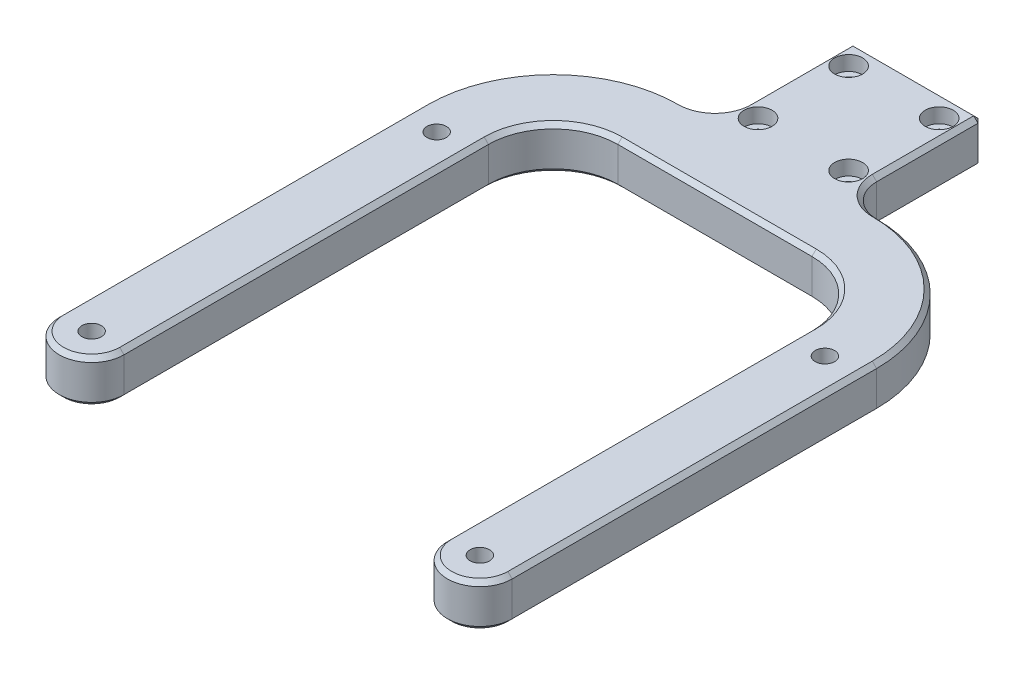
SolidWorks part; units mm, degrees
material "ABS PC"
ref_plane "Front Plane" through (0, 0, 0) normal (0, 0, 1) x (1, 0, 0)
ref_plane "Top Plane" through (0, 0, 0) normal (0, 1, 0) x (1, 0, 0)
ref_plane "Right Plane" through (0, 0, 0) normal (1, 0, 0) x (0, 0, -1)
sketch "Sketch1" plane through (0, 0, 0) normal (0, 1, 0) x (1, 0, 0)
  line L0 (22.5, 57.25) -> (0, 57.25)
  line L1 (0, 57.25) -> (0, 104.25)
  line L2 (37.5, 42.25) -> (37.5, -42.25)
  line L7 (15, 104.25) -> (0, 104.25)
  line L8 (0, 0) -> (0, 57.25) construction
  line L9 (15, 104.25) -> (15, 72.25)
  line L13 (15, 72.25) -> (22.5, 72.25)
  line L14 (52.5, 42.25) -> (52.5, -42.25)
  arc A4 (22.5, 57.25) -> (37.5, 42.25) centre (22.5, 42.25) cw
  arc A6 (22.5, 72.25) -> (52.5, 42.25) centre (22.5, 42.25) cw
  arc A9 (37.5, -42.25) -> (52.5, -42.25) centre (45, -42.25) ccw
  circle A10 centre (45, 37.75) radius 2.25
  circle A11 centre (45, -42.25) radius 2.25
  point P10 (37.5, 0)
  dimension "D7" = 80
  dimension "D8" = 30
  dimension "D9" = 15
  dimension "D6" = 107
  dimension "D14" = 4.5
  dimension "D1" = 15
  dimension "D2" = 15
  dimension "D3" = 32
  dimension "D4" = 30
  dimension "D5" = 75
extrude "Boss-Extrude1" add sketch "Sketch1" along normal blind 10
fillet "Fillet1" radius 7.5 1 edges at (15, 5, -72.25)
chamfer "Chamfer1" distance 1 angle 45 19 edges at (11.25, 0, -57.25) (33.1066, 0, -52.8566) (37.5, 0, 0) (52.5, 0, 0) (43.7132, 0, -63.4632) (15, 0, -92) (7.5, 0, -104.25) (11.25, 10, -57.25) (33.1066, 10, -52.8566) (37.5, 10, 0) (52.5, 10, 0) (43.7132, 10, -63.4632) (15, 10, -92) (7.5, 10, -104.25) (17.1967, 0, -74.4467) (17.1967, 10, -74.4467) (15, 5, -104.25) (45, 0, 49.75) (45, 10, 49.75)
sketch "Sketch5" plane through (0, 0, 0) normal (0, -1, 0) x (1, 0, 0)
  circle A0 centre (45, -37.75) radius 2.25 construction
  circle A1 centre (45, 42.25) radius 2.25 construction
  circle A2 centre (45, -37.75) radius 2.25
  circle A3 centre (45, 42.25) radius 2.25
extrude "Boss-Extrude2" add sketch "Sketch5" against normal offset from surface (4 mm away) 6 up to face at (26.0559, 10, -47.5059)
mirror "Mirror1" about plane through (0, 10, -57.25) normal (1, 0, 0) of bodies 104 101
sketch "Sketch6" plane through (0, 10, 0) normal (0, 1, 0) x (1, 0, 0)
  line L0 (-14, 104.25) -> (14, 104.25) construction
  line L1 (-15, 104.25) -> (15, 104.25) construction
  line L2 (-15, 104.25) -> (-15, 72.25) construction
  line L3 (-15, 72.25) -> (15, 72.25) construction
  line L4 (15, 104.25) -> (15, 72.25) construction
  line L5 (15, 103.25) -> (15, 79.75) construction
  line L7 (-10.5, 98.75) -> (10.5, 98.75) construction
  line L8 (-10.5, 98.75) -> (-10.5, 77.75) construction
  line L9 (-10.5, 77.75) -> (10.5, 77.75) construction
  line L10 (10.5, 98.75) -> (10.5, 77.75) construction
  circle A0 centre (10.5, 98.75) radius 1.5 construction
  circle A1 centre (10.5, 77.75) radius 1.5 construction
  circle A2 centre (-10.5, 98.75) radius 1.5 construction
  circle A3 centre (-10.5, 77.75) radius 1.5 construction
  point P14 (9.3511, 96.082)
  point P16 (10.0768, 96.3928)
  point P18 (-9.9047, 79.7384)
  point P19 (8.9398, 94.6811)
  point P20 (-10.1311, 75.2676)
  point P21 (-11.3576, 98.75)
  dimension "D3" = 3
  dimension "D4" = 18
  dimension "D5" = 4
  dimension "D6" = 3
  dimension "D1" = 30
  dimension "D2" = 32
hole_wizard "CBORE for M3 Hex Socket Head Cap Screw1" positions "Sketch7" profile "Sketch8" counterbore size "M3" standard "ISO" end condition through all
sketch "Sketch7" plane through (0, 10, 0) normal (0, 1, 0) x (1, 0, 0)
  point P0 (10.5, 98.75)
  point P3 (-10.5, 98.75)
  point P6 (-10.5, 77.75)
  point P9 (10.5, 77.75)
sketch "Sketch8" plane through (10.5, 10, -98.75) normal (1, 0, 0) x (0, 0, 1)
  line L0 (0, 0) -> (0, 10)
  line L1 (0, 10) -> (1.7, 10)
  line L3 (1.7, 10) -> (1.7, 3.4)
  line L4 (1.7, 3.4) -> (3.25, 3.4)
  line L5 (3.25, 3.4) -> (3.25, 0)
  line L7 (3.25, 0) -> (0, 0)
  line L11 (0, -6.35) -> (0, 107.95) construction
  dimension "Thru Hole Dia." = 3.4
  dimension "Thru Hole Depth" = 10
  dimension "C'Bore Dia." = 6.5
  dimension "C'Bore Depth" = 3.4
